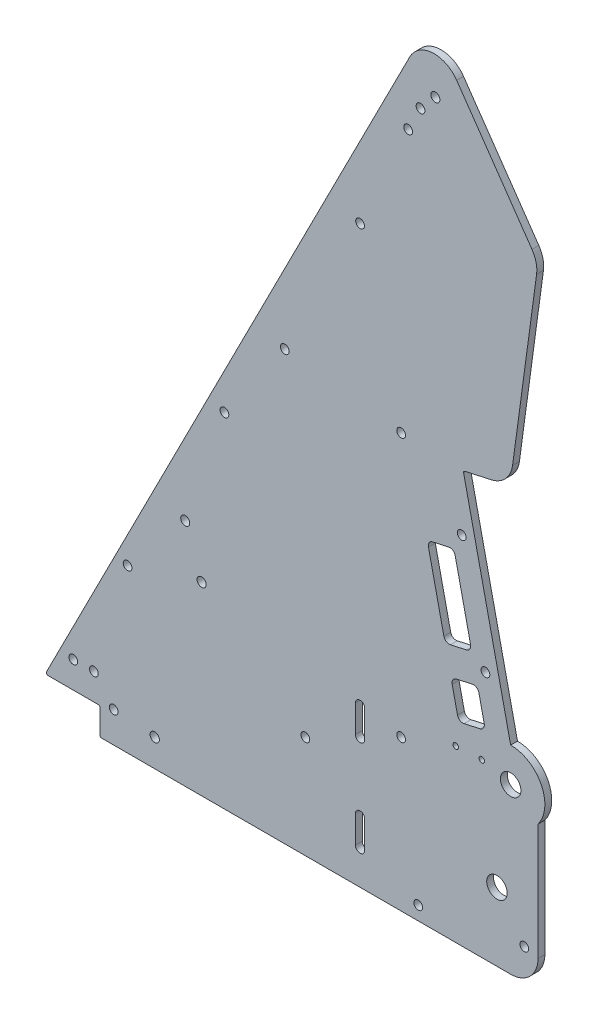
SolidWorks part; units mm, degrees
other "Markup1"
sketch "Sketch5"
ref_plane "Front Plane" through (0, 0, 0) normal (0, 0, 1) x (1, 0, 0)
ref_plane "Top Plane" through (0, 0, 0) normal (0, 1, 0) x (1, 0, 0)
ref_plane "Right Plane" through (0, 0, 0) normal (1, 0, 0) x (0, 0, -1)
sketch "Sketch1" plane through (0, 0, 0) normal (0, 0, 1) x (1, 0, 0)
  line L1 (228.6, -12.7) -> (228.6, 53.975)
  line L2 (178.7547, 351.4131) -> (0, 0)
  line L3 (228.6, 279.4) -> (178.7547, 351.4131)
  line L5 (0, 0) -> (25.4, 0)
  line L6 (25.4, 0) -> (25.4, -12.7)
  line L7 (25.4, -12.7) -> (228.6, -12.7)
  line L9 (215.9, 79.375) -> (193.9097, 178.5667)
  line L10 (193.9097, 178.5667) -> (215.6079, 183.377)
  line L11 (215.6079, 183.377) -> (228.6, 279.4)
  arc A0 (228.6, 53.975) -> (215.9, 79.375) centre (215.9, 63.5) ccw
  dimension "D7" = 12.7
  dimension "D8" = 76.2
  dimension "D10" = 31.75
  dimension "D2" = 292.1
  dimension "D3" = 25.4
  dimension "D4" = 215.9
  dimension "D5" = 394.2644
  dimension "D6" = 203.2
  dimension "D9" = 63.039
  dimension "D11" = 101.6
  dimension "D12" = 12.5
  dimension "D13" = 22.225
extrude "Boss-Extrude1" add sketch "Sketch1" along normal blind 3.175
sketch "Sketch2" plane through (0, 0, 3.175) normal (0, 0, 1) x (1, 0, 0)
  line L0 (178.7547, 351.4131) -> (0, 0) construction
  line L1 (25.4, -12.7) -> (228.6, -12.7) construction
  line L2 (215.9, 79.375) -> (193.9097, 178.5667) construction
  line L3 (193.9097, 178.5667) -> (215.6079, 183.377) construction
  line L4 (215.9, 79.375) -> (193.9097, 178.5667) construction
  line L5 (64.9432, 94.0578) -> (72.5445, 73.1732) construction
  line L6 (64.9432, 94.0578) -> (89.8317, 94.0578) construction
  line L10 (228.6, -12.7) -> (228.6, 53.975) construction
  circle A0 centre (64.9432, 94.0578) radius 2.0955
  circle A1 centre (180.975, 322.1643) radius 2.0955
  circle A2 centre (72.5445, 73.1732) radius 2.0955
  circle A3 centre (193.2078, 152.3944) radius 2.032
  circle A4 centre (215.9, 63.5) radius 4.7625
  circle A7 centre (173.0375, -6.35) radius 2.032
  circle A8 centre (204.203, 102.7985) radius 2.032
  circle A26 centre (209.55, 19.05) radius 4.7625
  arc A30 (228.6, 53.975) -> (215.9, 79.375) centre (215.9, 63.5) ccw construction
  circle A31 centre (165.1, 179.3875) radius 2.032
  dimension "D3" = 4.191
  dimension "D5" = 4.191
  dimension "D9" = 4.191
  dimension "D20" = 9.525
  dimension "D23" = 9.525
  dimension "D18" = 4.064
  dimension "D26" = 4.064
  dimension "D14" = 4.064
  dimension "D2" = 15.24
  dimension "D6" = 15.24
  dimension "D7" = 22.225
  dimension "D21" = 44.45
  dimension "D22" = 6.35
  dimension "D19" = 160.3375
  dimension "D24" = 44.45
  dimension "D25" = 6.35
  dimension "D27" = 25.4
  dimension "D28" = 50.8
  dimension "D29" = 6.35
  dimension "D17" = 6.35
  dimension "D33" = 55.5625
  dimension "D15" = 114.3
  dimension "D4" = 180.975
  dimension "D8" = 70
extrude "Cut-Extrude1" cut sketch "Sketch2" against normal through all
sketch "Sketch7" plane through (0, 0, 3.175) normal (0, 0, 1) x (1, 0, 0)
  line L0 (146.05, 3.175) -> (146.05, 15.875) construction
  line L1 (143.891, 3.175) -> (143.891, 15.875)
  line L2 (148.209, 3.175) -> (148.209, 15.875)
  line L3 (146.05, 47.625) -> (146.05, 60.325) construction
  line L4 (143.891, 47.625) -> (143.891, 60.325)
  line L5 (148.209, 47.625) -> (148.209, 60.325)
  line L6 (25.4, -12.7) -> (228.6, -12.7) construction
  line L12 (228.6, -12.7) -> (228.6, 53.975) construction
  line L13 (25.4, -12.7) -> (228.6, -12.7) construction
  arc A0 (143.891, 3.175) -> (148.209, 3.175) centre (146.05, 3.175) ccw
  arc A1 (148.209, 15.875) -> (143.891, 15.875) centre (146.05, 15.875) ccw
  arc A2 (143.891, 47.625) -> (148.209, 47.625) centre (146.05, 47.625) ccw
  arc A3 (148.209, 60.325) -> (143.891, 60.325) centre (146.05, 60.325) ccw
  circle A8 centre (50.8, 0) radius 2.159
  point P2 (146.05, 9.525)
  point P9 (146.05, 53.975)
  dimension "D1" = 4.318
  dimension "D5" = 4.318
  dimension "D2" = 12.7
  dimension "D3" = 12.7
  dimension "D4" = 44.45
  dimension "D6" = 95.25
  dimension "D7" = 82.55
  dimension "D8" = 15.875
  dimension "D9" = 12.7
extrude "Cut-Extrude2" cut sketch "Sketch7" against normal through all
sketch "Sketch10" plane through (0, 0, 3.175) normal (0, 0, 1) x (1, 0, 0)
  circle A1 centre (165.1, 57.15) radius 2.032
  circle A2 centre (120.65, 34.925) radius 2.032
  circle A3 centre (13.0465, 12.3347) radius 2.032
  circle A4 centre (22.5715, 12.3347) radius 2.032
  circle A5 centre (38.2114, 62.6398) radius 2.032
  dimension "D1" = 4.064
  dimension "D2" = 4.064
  dimension "D4" = 63.5
  dimension "D5" = 69.85
extrude "Cut-Extrude3" cut sketch "Sketch10" against normal up to next
fillet "Fillet1" radius 12.7 4 edges at (228.6, -12.7, 1.5875) (178.7547, 351.4131, 1.5875) (215.6079, 183.377, 1.5875) (228.6, 279.4, 1.5875)
fillet "Fillet2" radius 0.7937 4 edges at (25.4, -12.7, 1.5875) (25.4, 0, 1.5875) (193.9097, 178.5667, 1.5875) (0, 0, 1.5875)
sketch "Sketch12" plane through (0, 0, 3.175) normal (0, 0, 1) x (1, 0, 0)
  circle A0 centre (31.75, 1.5875) radius 2.032
  circle A1 centre (222.25, 1.5875) radius 2.032
  dimension "D1" = 4.064
extrude "Cut-Extrude5" cut sketch "Sketch12" against normal through all
sketch "Sketch13" plane through (0, 0, 3.175) normal (0, 0, 1) x (1, 0, 0)
  line L0 (189.6226, 145.0954) -> (197.869, 107.8985)
  line L1 (177.2237, 142.3466) -> (185.47, 105.1497)
  line L2 (215.9, 79.375) -> (194.0815, 177.7917) construction
  line L3 (185.47, 105.1497) -> (197.869, 107.8985)
  line L4 (177.2237, 142.3466) -> (189.6226, 145.0954)
  line L5 (194.6847, 178.7385) -> (206.9592, 181.4597) construction
  line L6 (190.4268, 66.2609) -> (202.5335, 66.7895) construction
  line L7 (188.2188, 92.7508) -> (200.6178, 95.4995)
  line L8 (188.2188, 92.7508) -> (191.7922, 76.6321)
  line L9 (191.7922, 76.6321) -> (204.1912, 79.3809)
  line L10 (200.6178, 95.4995) -> (204.1912, 79.3809)
  line L11 (190.4268, 66.2609) -> (191.7922, 76.6321) construction
  line L12 (202.5335, 66.7895) -> (204.1912, 79.3809) construction
  circle A0 centre (190.4268, 66.2609) radius 1.27
  circle A1 centre (202.5335, 66.7895) radius 1.27
  point P3 (193.7458, 126.4969)
  point P6 (181.3468, 123.7481)
  dimension "D7" = 2.54
  dimension "D1" = 38.1
  dimension "D2" = 12.7
  dimension "D3" = 11.43
  dimension "D4" = 50.8
  dimension "D5" = 16.51
  dimension "D6" = 12.7
  dimension "D8" = 110
  dimension "D9" = 80
  dimension "D10" = 12.7
extrude "Cut-Extrude6" cut sketch "Sketch13" against normal through all both and the other way through all
sketch "Sketch14" plane through (0, 0, 3.175) normal (0, 0, 1) x (1, 0, 0)
  line L0 (26.1937, -12.7) -> (215.9, -12.7) construction
  line L1 (228.6, 0) -> (228.6, 53.975) construction
  circle A0 centre (146.05, 254) radius 2.032
  circle A1 centre (111.125, 186.055) radius 2.032
  dimension "D1" = 4.064
  dimension "D2" = 198.755
  dimension "D3" = 117.475
  dimension "D4" = 82.55
  dimension "D5" = 266.7
extrude "Cut-Extrude7" cut sketch "Sketch14" against normal up to next
sketch "Sketch15" plane through (0, 0, 3.175) normal (0, 0, 1) x (1, 0, 0)
  line L0 (169.1053, 332.4434) -> (0.5868, 1.1536) construction
  circle A0 centre (83.1368, 146.6315) radius 2.032
  circle A1 centre (174.0994, 314.25) radius 2.032
  circle A2 centre (168.3414, 302.9303) radius 2.032
  circle A3 centre (174.0994, 314.25) radius 1.905 construction
  circle A4 centre (168.3414, 302.9303) radius 1.905 construction
  dimension "D1" = 4.064
  dimension "D4" = 4.064
  dimension "D2" = 7.62
  dimension "D3" = 82.55
extrude "Cut-Extrude8" cut sketch "Sketch15" against normal through all
fillet "Fillet3" radius 2.54 8 edges at (177.2237, 142.3466, 1.5875) (189.6226, 145.0954, 1.5875) (197.869, 107.8985, 1.5875) (185.47, 105.1497, 1.5875) (200.6178, 95.4995, 1.5875) (188.2188, 92.7508, 1.5875) (191.7922, 76.6321, 1.5875) (204.1912, 79.3809, 1.5875)
equation "\"D6@Sketch2\"=\"D2@Sketch2\""
